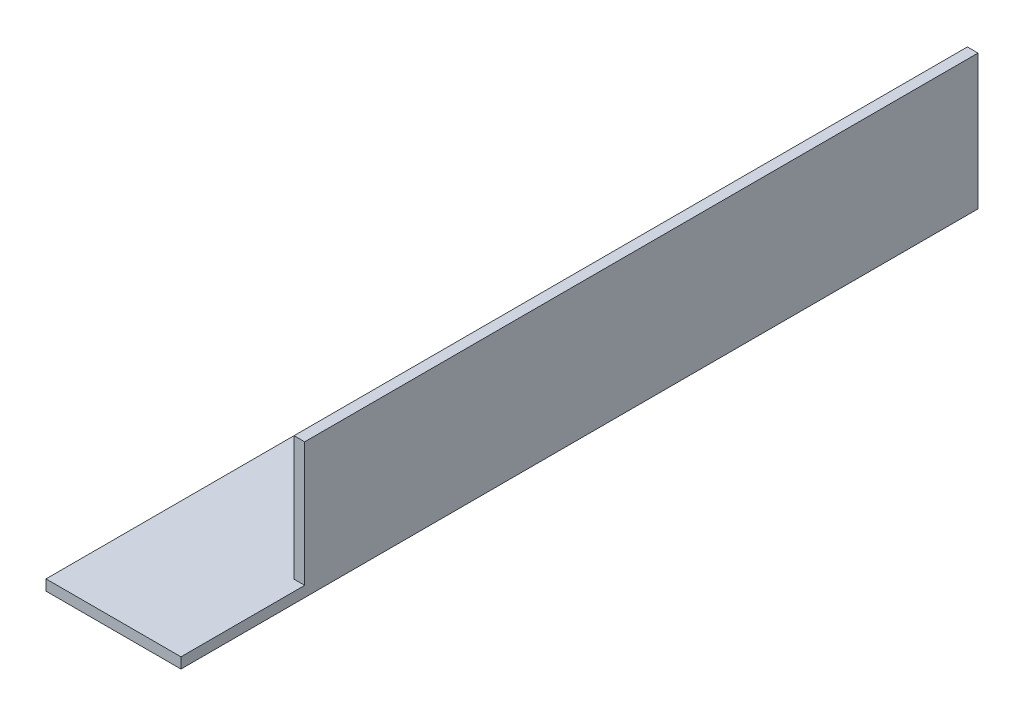
SolidWorks part; units mm, degrees
material "Acrylic (Medium-high impact)"
ref_plane "Front Plane" through (0, 0, 0) normal (0, 0, 1) x (1, 0, 0)
ref_plane "Top Plane" through (0, 0, 0) normal (0, 1, 0) x (1, 0, 0)
ref_plane "Right Plane" through (0, 0, 0) normal (1, 0, 0) x (0, 0, -1)
ref_axis "Axis1" through (0, -55, 0) along (0, 1, 0)
sketch "Sketch1" plane through (0, 0, 0) normal (0, 0, 1) x (1, 0, 0)
  line L0 (0, 25.4) -> (0, 0)
  line L1 (0, -55) -> (0, 55) construction
  line L2 (0, 0) -> (-25.4, 0)
  dimension "D1" = 25.4
  dimension "D2" = 25.4
extrude "Extrude-Thin1" add sketch "Sketch1" along normal blind 150 thin thin type one direction wall 2
sketch "Sketch2" plane through (0, 0, 0) normal (1, 0, 0) x (0, 0, -1)
  line L0 (-126.7145, 25.4) -> (-126.7145, 2) construction
  line L1 (-126.7145, 2) -> (-150.1145, 2) construction
  line L2 (-126.7145, 33.5854) -> (-126.7145, 2)
  line L3 (-126.7145, 2) -> (-171.8332, 2)
  line L4 (-126.7145, 33.5854) -> (-171.8332, 33.5854)
  line L5 (-171.8332, 33.5854) -> (-171.8332, 2)
  dimension "D1" = 45.1187
  dimension "D2" = 31.5854
extrude "Cut-Extrude1" cut sketch "Sketch2" against normal blind 29
